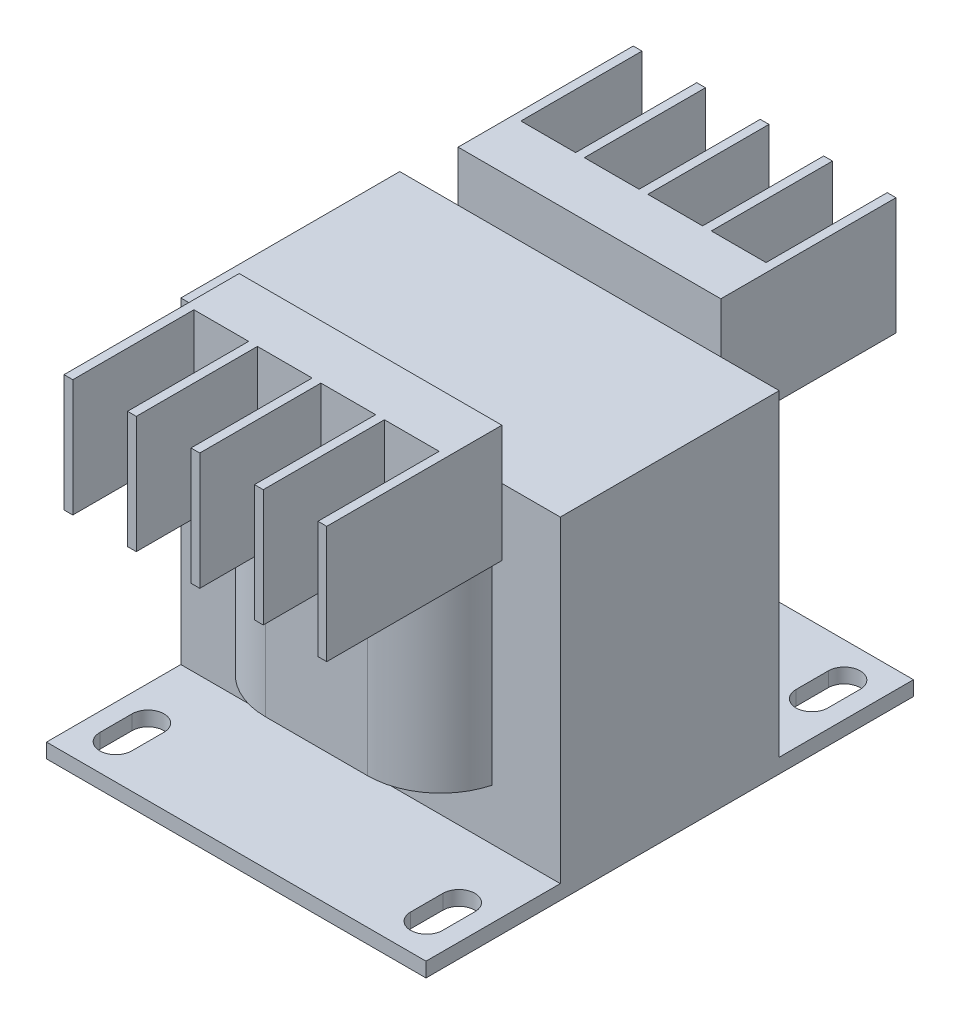
SolidWorks part; units mm, degrees
ref_plane "Front" through (0, 0, 0) normal (0, 0, 1) x (1, 0, 0)
ref_plane "Top" through (0, 0, 0) normal (0, 1, 0) x (1, 0, 0)
ref_plane "Right" through (0, 0, 0) normal (1, 0, 0) x (0, 0, -1)
sketch "Sketch1" plane through (0, 0, 0) normal (0, 1, 0) x (1, 0, 0)
  line L1 (-33.02, -42.418) -> (33.02, -42.418)
  line L2 (-33.02, -42.418) -> (-33.02, 42.418)
  line L3 (-33.02, 42.418) -> (33.02, 42.418)
  line L4 (33.02, -42.418) -> (33.02, 42.418)
  line L5 (-33.02, -42.418) -> (33.02, 42.418) construction
  line L6 (-33.02, 42.418) -> (33.02, -42.418) construction
  point P0 (0, 0)
  dimension "D1" = 66.04
  dimension "D2" = 84.836
extrude "Boss-Extrude1" add sketch "Sketch1" along normal blind 2.54
hole_wizard "7/32 (0.21875) Diameter Slot1" positions "Sketch2" profile "Sketch3" size "7/32" standard "ANSI Inch" slot yes end condition up to next
sketch "Sketch2" plane through (0, 2.54, 0) normal (0, 1, 0) x (1, 0, 0)
  line L0 (-27.051, 27.94) -> (-27.051, 39.116) construction
  line L1 (-27.051, -33.528) -> (-27.051, 33.528) construction
  line L2 (-27.051, 33.528) -> (27.051, 33.528) construction
  line L3 (27.051, 33.528) -> (27.051, -33.528) construction
  line L4 (27.051, -33.528) -> (-27.051, -33.528) construction
  line L6 (-27.051, 33.528) -> (27.051, -33.528) construction
  point P0 (-27.051, 33.528)
  point P4 (27.051, 33.528)
  point P6 (27.051, -33.528)
  point P8 (-27.051, -33.528)
  dimension "D1" = 11.176
  dimension "D2" = 67.056
  dimension "D3" = 54.102
sketch "Sketch3" plane through (-27.051, 2.54, -33.528) normal (1, 0, 0) x (0, 0, 1)
  line L0 (0, 0) -> (0, 2.54)
  line L1 (0, 2.54) -> (2.7781, 2.54)
  line L2 (2.7781, 2.54) -> (2.7781, 0)
  line L5 (2.7781, 0) -> (0, 0)
  line L11 (0, -6.35) -> (0, 107.95) construction
  dimension "Thru Hole Dia." = 5.5562
  dimension "Thru Hole Depth" = 2.54
sketch "Sketch4" plane through (0, 2.54, 0) normal (0, 1, 0) x (1, 0, 0)
  line L0 (33.02, -42.418) -> (33.02, 42.418) construction
  line L1 (-33.02, -19.05) -> (33.02, -19.05)
  line L2 (-33.02, -19.05) -> (-33.02, 19.05)
  line L3 (-33.02, 19.05) -> (33.02, 19.05)
  line L4 (33.02, -19.05) -> (33.02, 19.05)
  line L5 (-33.02, -19.05) -> (33.02, 19.05) construction
  line L6 (-33.02, 19.05) -> (33.02, -19.05) construction
  point P0 (0, 0)
  dimension "D1" = 38.1
extrude "Boss-Extrude2" add sketch "Sketch4" along normal blind 55.245
ref_plane "Plane1" through (0, 11.43, 0) normal (0, 1, 0) x (1, 0, 0)
sketch "Sketch5" plane through (0, 11.43, 0) normal (0, 1, 0) x (1, 0, 0)
  line L0 (-21.59, 15.748) -> (-21.59, -15.748)
  line L1 (-8.89, -28.448) -> (8.89, -28.448)
  line L2 (21.59, -15.748) -> (21.59, 15.748)
  line L3 (8.89, 28.448) -> (-8.89, 28.448)
  line L4 (-8.89, 15.748) -> (8.89, -15.748) construction
  line L5 (8.89, -15.748) -> (-8.89, -15.748) construction
  line L6 (-8.89, -15.748) -> (8.89, 15.748) construction
  line L7 (8.89, 15.748) -> (-8.89, 15.748) construction
  arc A0 (-21.59, -15.748) -> (-8.89, -28.448) centre (-8.89, -15.748) ccw
  arc A1 (8.89, -28.448) -> (21.59, -15.748) centre (8.89, -15.748) ccw
  arc A2 (21.59, 15.748) -> (8.89, 28.448) centre (8.89, 15.748) ccw
  arc A3 (-8.89, 28.448) -> (-21.59, 15.748) centre (-8.89, 15.748) ccw
  dimension "D1" = 56.896
  dimension "D2" = 12.7
  dimension "D3" = 43.18
extrude "Boss-Extrude3" add sketch "Sketch5" along normal blind 34.7218
sketch "Sketch6" plane through (0, 46.1518, 0) normal (0, 1, 0) x (1, 0, 0)
  line L0 (22.86, -19.05) -> (-22.86, -19.05)
  line L1 (-33.02, -19.05) -> (33.02, -19.05) construction
  line L2 (-22.86, -19.05) -> (-22.86, -49.53)
  line L3 (-22.86, -49.53) -> (-21.336, -49.53)
  line L4 (-21.336, -49.53) -> (-21.336, -28.448)
  line L5 (-21.336, -28.448) -> (-11.811, -28.448)
  line L6 (-11.811, -28.448) -> (-11.811, -49.53)
  line L7 (-11.811, -49.53) -> (-10.287, -49.53)
  line L8 (-10.287, -49.53) -> (-10.287, -28.448)
  line L9 (-10.287, -28.448) -> (-0.762, -28.448)
  line L10 (-0.762, -28.448) -> (-0.762, -49.53)
  line L11 (-0.762, -49.53) -> (0.762, -49.53)
  line L12 (0.762, -49.53) -> (0.762, -28.448)
  line L13 (0.762, -28.448) -> (10.287, -28.448)
  line L14 (10.287, -28.448) -> (10.287, -49.53)
  line L15 (10.287, -49.53) -> (11.811, -49.53)
  line L16 (11.811, -49.53) -> (11.811, -28.448)
  line L17 (11.811, -28.448) -> (21.336, -28.448)
  line L18 (21.336, -28.448) -> (21.336, -49.53)
  line L19 (21.336, -49.53) -> (22.86, -49.53)
  line L20 (22.86, -49.53) -> (22.86, -19.05)
  line L21 (21.336, -49.53) -> (11.811, -49.53) construction
  line L22 (10.287, -49.53) -> (0.762, -49.53) construction
  line L23 (-0.762, -49.53) -> (-10.287, -49.53) construction
  line L24 (-11.811, -49.53) -> (-21.336, -49.53) construction
  line L25 (0, 0) -> (0, -19.05) construction
  dimension "D1" = 45.72
  dimension "D2" = 49.53
  dimension "D3" = 9.398
  dimension "D4" = 1.524
extrude "Boss-Extrude4" add sketch "Sketch6" along normal offset from surface (20.3962 mm away) 8.763 up to face at (0, 57.785, 0) offset beyond the face yes
mirror "Mirror1" about plane through (0, 0, 0) normal (0, 0, 1) of "Boss-Extrude4"
